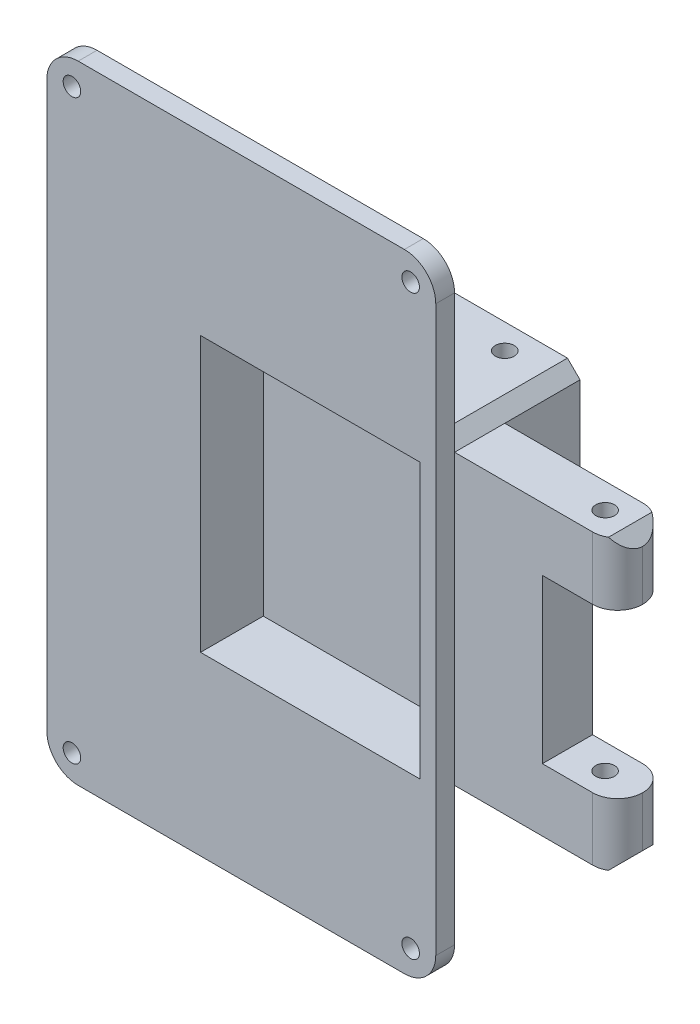
SolidWorks part; units mm, degrees
ref_plane "前视基准面" through (0, 0, 0) normal (0, 0, 1) x (1, 0, 0)
ref_plane "上视基准面" through (0, 0, 0) normal (0, 1, 0) x (1, 0, 0)
ref_plane "右视基准面" through (0, 0, 0) normal (1, 0, 0) x (0, 0, -1)
other "Configuration Table"
sketch "草图1" plane through (0, 0, 0) normal (0, 0, 1) x (1, 0, 0)
  line L1 (-20, 25) -> (20, 25)
  line L2 (-20, 25) -> (-20, -25)
  line L3 (-20, -25) -> (20, -25)
  line L4 (20, 25) -> (20, -25)
  line L5 (-20, 25) -> (20, -25) construction
  line L6 (-20, -25) -> (20, 25) construction
  line L7 (-17.5, 21.875) -> (17.5, 21.875)
  line L8 (-17.5, 21.875) -> (-17.5, -21.875)
  line L9 (-17.5, -21.875) -> (17.5, -21.875)
  line L10 (17.5, 21.875) -> (17.5, -21.875)
  line L11 (-17.5, 21.875) -> (17.5, -21.875) construction
  line L12 (-17.5, -21.875) -> (17.5, 21.875) construction
  point P0 (0, 0)
  point P6 (0, 0)
  dimension "D1" = 40
  dimension "D2" = 50
  dimension "D3" = 35
extrude "凸台-拉伸1" add sketch "草图1" along normal blind 20
chamfer "倒角1" distance 2 angle 45 4 edges at (-20, -25, 10) (20, -25, 10) (-20, 25, 10) (20, 25, 10)
sketch "草图4" plane through (0, 25, 0) normal (0, 1, 0) x (1, 0, 0)
  line L0 (18, 0) -> (-18, 0) construction
  line L1 (-20, -20) -> (-20, 0) construction
  circle A0 centre (-12, -4) radius 1.5
  circle A1 centre (0, -4) radius 1.5
  circle A2 centre (12, -4) radius 1.5
  dimension "D1" = 3
  dimension "D2" = 4
  dimension "D3" = 8
  dimension "D4" = 2
  dimension "D5" = 2
extrude "切除-拉伸3" cut sketch "草图4" against normal blind 6
sketch "草图7" plane through (20, 0, 0) normal (1, 0, 0) x (0, 0, -1)
  line L0 (0, 23) -> (-20, 23) construction
  line L1 (-20, -23) -> (-12, -23)
  line L2 (-20, -23) -> (-20, 23)
  line L3 (-20, 23) -> (-12, 23)
  line L4 (-12, -23) -> (-12, 23)
  dimension "D1" = 8
extrude "凸台-拉伸2" add sketch "草图7" along normal blind 26
sketch "草图8" plane through (46, 0, 0) normal (1, 0, 0) x (0, 0, -1)
  line L0 (-12, 23) -> (-20, 23) construction
  line L3 (-12, -23) -> (-12, 23) construction
  line L5 (-20, 13) -> (-20, -13)
  line L6 (-20, -13) -> (-12, -13)
  line L7 (-12, 13) -> (-12, -13)
  line L8 (-20, 13) -> (-12, 13)
  dimension "D1" = 26
  dimension "D2" = 10
  dimension "D3" = 8
extrude "切除-拉伸5" cut sketch "草图8" against normal blind 12
chamfer "倒角2" distance 2 angle 45 2 edges at (46, -23, 16) (46, 23, 16)
fillet "圆角1" radius 4 4 edges at (46, -17, 12) (46, -17, 20) (46, 17, 12) (46, 17, 20)
sketch "草图9" plane through (0, -23, 0) normal (0, -1, 0) x (1, 0, 0)
  line L0 (20, 16) -> (44, 16) construction
  line L1 (20, 20) -> (20, 12) construction
  line L2 (44, 12.5359) -> (44, 19.4641) construction
  circle A0 centre (40, 16) radius 1.5
  dimension "D2" = 3
  dimension "D1" = 20
extrude "切除-拉伸6" cut sketch "草图9" against normal through all both and the other way through all
sketch "草图10" plane through (0, 0, 0) normal (0, 0, -1) x (-1, 0, 0)
  line L1 (-17.5, 21.875) -> (17.5, 21.875)
  line L2 (-17.5, 21.875) -> (-17.5, -21.875)
  line L3 (-17.5, -21.875) -> (17.5, -21.875)
  line L4 (17.5, 21.875) -> (17.5, -21.875)
extrude "凸台-拉伸4" add sketch "草图10" against normal blind 2
sketch "草图11" plane through (0, 0, 20) normal (0, 0, 1) x (1, 0, 0)
  line L0 (-42, 0) -> (20, 0) construction
  line L1 (20, 50) -> (-42, 50)
  line L2 (20, 50) -> (20, -50)
  line L3 (20, -50) -> (-42, -50)
  line L4 (-42, 50) -> (-42, -50)
  line L5 (20, 13) -> (20, -13) construction
  line L7 (-17.5, 21.875) -> (17.5, 21.875)
  line L8 (-17.5, 21.875) -> (-17.5, -21.875)
  line L9 (-17.5, -21.875) -> (17.5, -21.875)
  line L10 (17.5, 21.875) -> (17.5, -21.875)
  circle A0 centre (-38, 46) radius 1.4
  circle A1 centre (16, 46) radius 1.4
  circle A2 centre (-38, -46) radius 1.4
  circle A3 centre (16, -46) radius 1.4
  dimension "D4" = 2.8
  dimension "D6" = 2.8
  dimension "D9" = 2.8
  dimension "D10" = 2.8
  dimension "D1" = 100
  dimension "D2" = 62
  dimension "D3" = 4
  dimension "D5" = 4
  dimension "D7" = 4
  dimension "D8" = 4
  dimension "D11" = 4
  dimension "D12" = 4
  dimension "D13" = 4
  dimension "D14" = 4
extrude "凸台-拉伸5" add sketch "草图11" along normal blind 3
fillet "圆角2" radius 5 4 edges at (20, 50, 21.5) (-42, 50, 21.5) (-42, -50, 21.5) (20, -50, 21.5)
sketch "草图12" plane through (0, 0, 2) normal (0, 0, 1) x (1, 0, 0)
  line L1 (-17.5, 21.875) -> (17.5, 21.875)
  line L2 (-17.5, 21.875) -> (-17.5, -21.875)
  line L3 (-17.5, -21.875) -> (17.5, -21.875)
  line L4 (17.5, 21.875) -> (17.5, -21.875)
extrude "凸台-拉伸6" add sketch "草图12" along normal blind 11
sketch "草图5" plane through (0, -25, 0) normal (0, -1, 0) x (1, 0, 0)
  line L1 (-20, 0) -> (-20, 20) construction
  line L2 (-18, 0) -> (18, 0) construction
  circle A0 centre (-12, 4) radius 1.5
  circle A1 centre (0, 4) radius 1.5
  circle A2 centre (12, 4) radius 1.5
  dimension "D1" = 3
  dimension "D2" = 4
  dimension "D3" = 8
  dimension "D4" = 2
  dimension "D5" = 2
extrude "切除-拉伸4" cut sketch "草图5" against normal up to next and the other way through all
